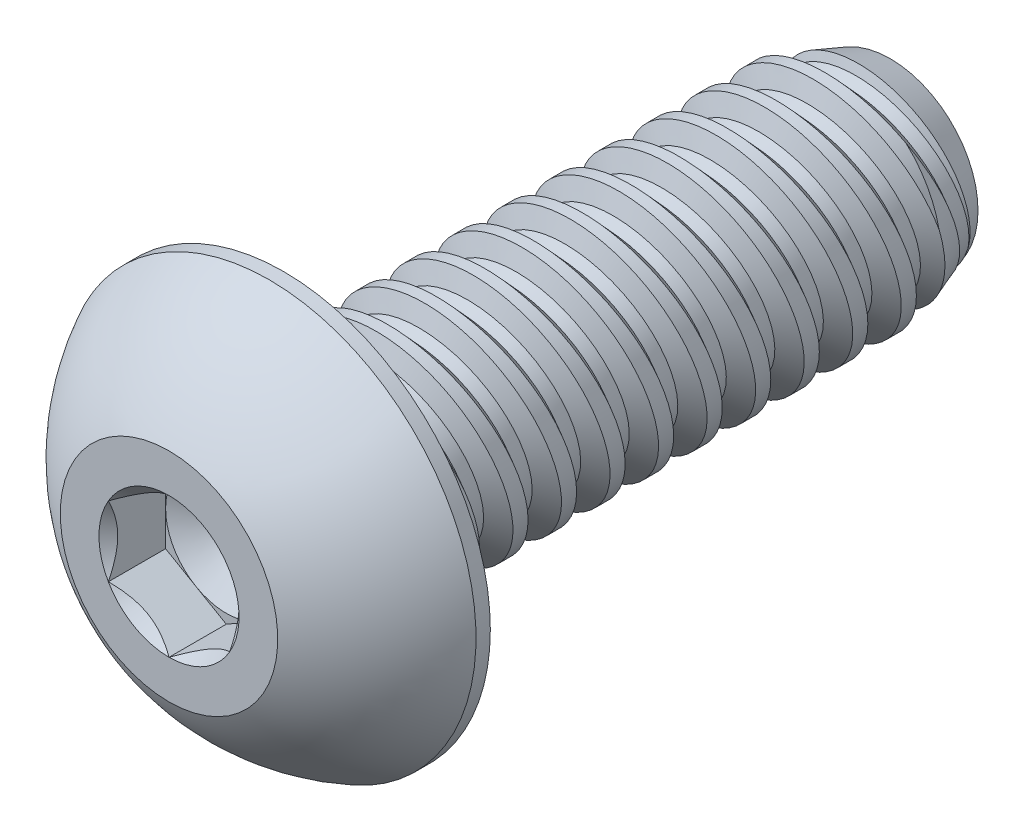
SolidWorks part; units mm, degrees
material "Alloy Steel"
ref_plane "Front" through (0, 0, 0) normal (0, 0, 1) x (1, 0, 0)
ref_plane "Top" through (0, 0, 0) normal (0, 1, 0) x (1, 0, 0)
ref_plane "Right" through (0, 0, 0) normal (1, 0, 0) x (0, 0, -1)
sketch "Sketch1" plane through (0, 0, 0) normal (1, 0, 0) x (0, 0, -1)
  line L0 (0, 0) -> (-1.4986, 0) construction
  line L1 (0, 0) -> (7.9375, 0)
  line L2 (0, 0) -> (0, 1.4224)
  line L3 (0, 1.4224) -> (7.9375, 1.4224)
  line L4 (7.9375, 0) -> (7.9375, 1.4224)
  line L5 (0, -1.4224) -> (7.9375, -1.4224) construction
  dimension "D1" = 7.9375
  dimension "Thread Dia" = 2.8448
  dimension "Length" = 7.9375
  dimension "Head Height" = 1.4986
revolve "Revolve1" add sketch "Sketch1" angle 360 about L0
ref_plane "Plane1" through (0, 0, 1.4986) normal (0, 0, 1) x (1, 0, 0)
sketch "Sketch2" plane through (0, 0, 0) normal (1, 0, 0) x (0, 0, -1)
  line L0 (0, 1.4224) -> (0, -1.4224) construction
  line L1 (0, -1.4224) -> (0.635, -1.4224) construction
  line L2 (0.635, -1.4224) -> (0, 1.4224) construction
  line L3 (0, 1.4224) -> (0.0775, 1.4397) construction
  line L4 (0.0775, 1.4397) -> (0.6197, 1.5607)
  line L5 (0.6197, 1.5607) -> (0.501, 1.1821)
  line L6 (0.501, 1.1821) -> (0.346, 1.1475)
  line L7 (0.346, 1.1475) -> (0.0775, 1.4397)
  line L8 (0.4235, 1.1648) -> (0.3486, 1.5002) construction
  line L9 (0, -1.4224) -> (7.9375, -1.4224) construction
  line L10 (0, 1.4224) -> (7.9375, 1.4224) construction
  line L12 (0.366, 1.4224) -> (1.001, -1.4224) construction
  line L13 (0, -0.1526) -> (1.367, 0.1526) construction
  line L15 (0, 0) -> (0, 1.4224) construction
  point P19 (0.6835, 0)
  dimension "D1" = 60
  dimension "Thread Pitch" = 0.635
  dimension "D2" = 0.0794
  dimension "D3" = 0.1588
  dimension "D4" = 0.635
revolve "Cut-Revolve1" cut sketch "Sketch2" angle 360 about L13
sketch "Sketch3" plane through (0, 0, 0) normal (1, 0, 0) x (0, 0, -1)
  line L0 (7.9375, 1.1475) -> (7.1821, 1.4224)
  line L1 (7.1821, 1.4224) -> (7.9375, 1.4224)
  line L2 (7.9375, 1.4224) -> (7.9375, 1.1475)
  line L3 (0, 1.4224) -> (7.9375, 1.4224) construction
  line L4 (7.9375, 0) -> (7.9375, 1.4224) construction
  line L5 (7.1821, 0) -> (0, 0) construction
  line L6 (7.1821, 1.4224) -> (7.1821, -1.4224) construction
  line L7 (0, -1.4224) -> (7.9375, -1.4224) construction
  dimension "D1" = 20
  dimension "D2" = 2.8448
revolve "Cut-Revolve2" cut sketch "Sketch3" angle 360 about L5
pattern_linear "LPattern1" count 13 spacing 0.635 along (0, 0, 1)
pattern_linear "LPattern2" count 2 spacing 0.635 along (0, 0, 1)
sketch "Sketch4" plane through (0, 0, 0) normal (0, 0, 1) x (1, 0, 0)
  circle A0 centre (0, 0) radius 2.7051
  dimension "Head Dia" = 5.4102
extrude "Extrude1" add sketch "Sketch4" along normal up to surface (1.4986 mm away)
sketch "Sketch9" plane through (0, 0, 0) normal (1, 0, 0) x (0, 0, -1)
  line L0 (0, 2.7051) -> (-0.1873, 2.7051)
  line L1 (0, 2.7051) -> (0, 2.8924)
  line L2 (0, 2.8924) -> (-1.6859, 2.8924)
  line L3 (0, 0) -> (-1.4986, 0) construction
  line L4 (-1.6859, 2.8924) -> (-1.6859, 1.4224)
  line L5 (-1.6859, 1.4224) -> (-1.4986, 1.4224)
  line L6 (0, 0) -> (0, 1.4224) construction
  line L10 (0, 2.7051) -> (-1.4986, 2.7051) construction
  line L11 (0, 1.4224) -> (7.9375, 1.4224) construction
  line L12 (-1.4986, 2.7051) -> (-1.4986, -2.7051) construction
  arc A0 (-1.4986, 1.4224) -> (-0.1873, 2.7051) centre (1.1758, 0) cw
  dimension "Side Head Height" = 0.1873
revolve "Cut-Revolve3" cut sketch "Sketch9" angle 360 about L3
sketch "Sketch6" plane through (0, 0, 1.4986) normal (0, 0, 1) x (1, 0, 0)
  line L1 (0, -0.9165) -> (0.7937, -0.4583)
  line L2 (0.7937, -0.4583) -> (0.7937, 0.4583)
  line L3 (0.7937, 0.4583) -> (0, 0.9165)
  line L4 (0, 0.9165) -> (-0.7938, 0.4583)
  line L5 (-0.7938, 0.4583) -> (-0.7938, -0.4583)
  line L6 (-0.7938, -0.4583) -> (0, -0.9165)
  circle A0 centre (0, 0) radius 0.7938 construction
  dimension "Hex" = 1.5875
extrude "Cut-Extrude1" cut sketch "Sketch6" against normal blind 0.7493
sketch "Sketch7" plane through (0, 0, 1.4986) normal (0, 0, 1) x (1, 0, 0)
  circle A0 centre (0, 0) radius 0.9165
extrude "Cut-Extrude4" cut sketch "Sketch7" against normal blind 0.7493 draft 45
sketch "Sketch8" plane through (0, 0, 0.7493) normal (0, 0, 1) x (1, 0, 0)
  circle A0 centre (0, 0) radius 0.7938 construction
  circle A1 centre (0, 0) radius 0.7938
extrude "Cut-Extrude5" cut sketch "Sketch8" against normal blind 0.2498 draft 60
equation "\"D2@Sketch2\"=\"Thread Pitch@Sketch2\"/8"
equation "\"D3@Sketch2\"=\"Thread Pitch@Sketch2\"/4"
equation "\"D4@Sketch2\"=\"Thread Pitch@Sketch2\""
equation "\"D3@LPattern1\"=\"Thread Pitch@Sketch2\""
equation "\"D1@Cut-Extrude1\"=\"Head Height@Sketch1\"/2"
equation "\"D1@Cut-Extrude4\"=\"D1@Cut-Extrude1\""
equation "\"D1@Cut-Extrude5\"=\"D1@Cut-Extrude1\"/3"
equation "\"D1@LPattern1\"=\"D1@Sketch1\"/\"Thread Pitch@Sketch2\""
equation "\"D3@LPattern2\"=\"Thread Pitch@Sketch2\""
equation "\"Side Head Height@Sketch9\"=\"Head Height@Sketch1\"/8"
